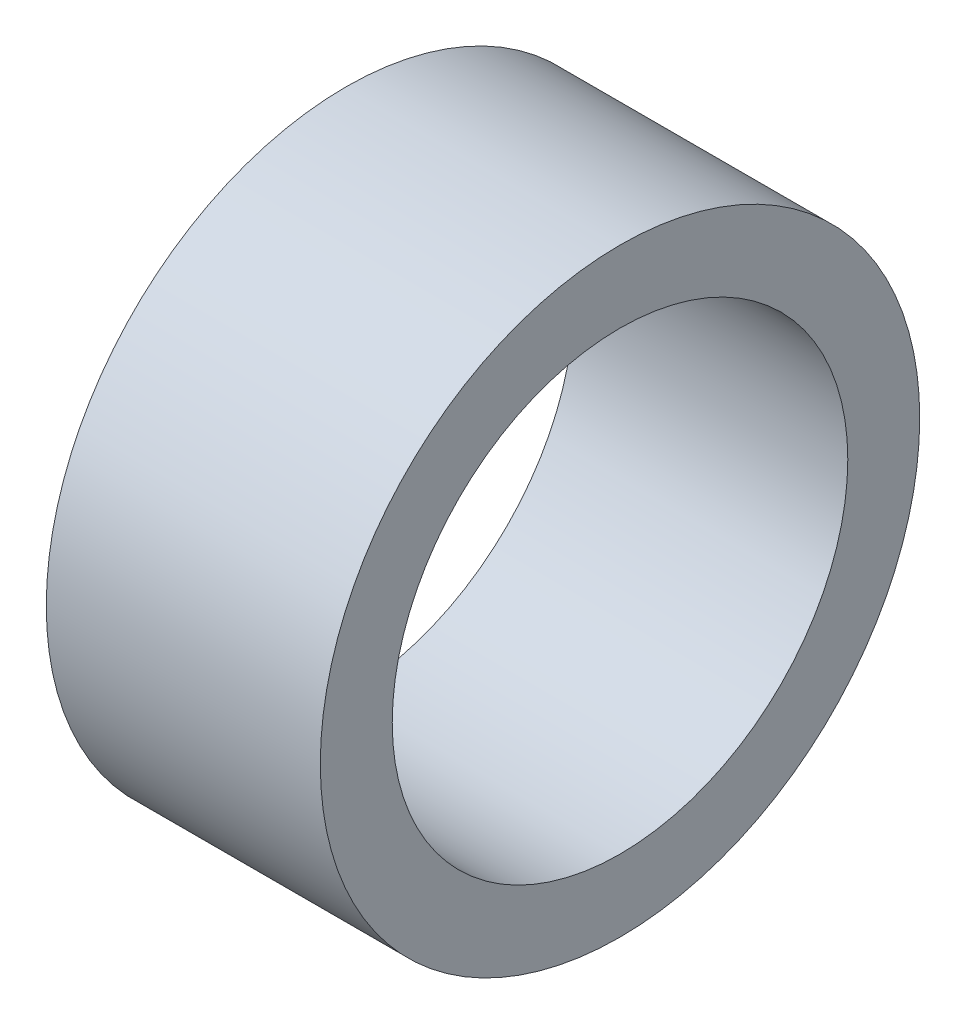
SolidWorks part; units mm, degrees
material "Nylon 6/10"
ref_plane "Front Plane" through (0, 0, 0) normal (0, 0, 1) x (1, 0, 0)
ref_plane "Top Plane" through (0, 0, 0) normal (0, 1, 0) x (1, 0, 0)
ref_plane "Right Plane" through (0, 0, 0) normal (1, 0, 0) x (0, 0, -1)
sketch "Sketch1" plane through (0, 0, 0) normal (0, 0, 1) x (1, 0, 0)
  line L0 (38.1, -13.4791) -> (38.1, 11.7806) construction
  line L1 (38.1, 5.5563) -> (43.18, 5.5563)
  line L2 (38.1, 5.5563) -> (38.1, 4.2228)
  line L3 (38.1, 4.2228) -> (43.18, 4.2228)
  line L4 (43.18, 5.5563) -> (43.18, 4.2228)
  line L5 (0, 0) -> (42.6651, 0) construction
  line L7 (44.1854, 3.9688) -> (-54.7878, 3.9688) construction
  dimension "D1" = 0.254
  dimension "D2" = 11.1125
  dimension "D3" = 5.08
revolve "Revolve1" add sketch "Sketch1" angle 360 about L5
